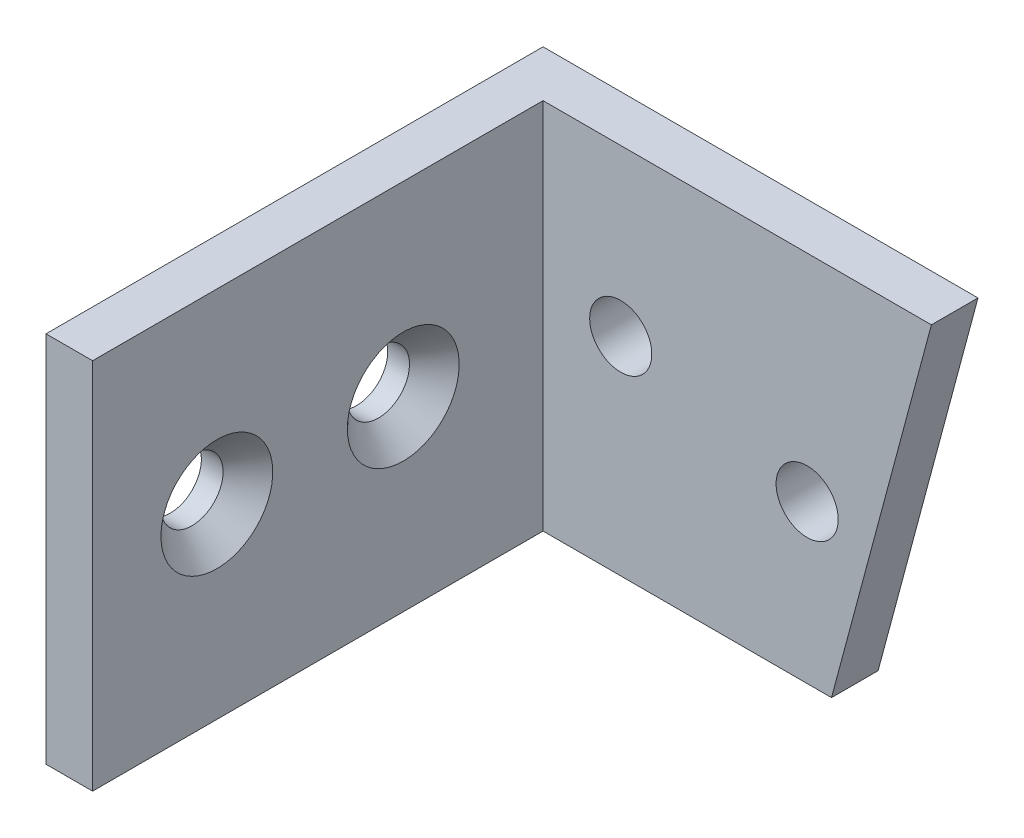
SolidWorks part; units mm, degrees
material "6061 Alloy"
ref_plane "Front Plane" through (0, 0, 0) normal (0, 0, 1) x (1, 0, 0)
ref_plane "Top Plane" through (0, 0, 0) normal (0, 1, 0) x (1, 0, 0)
ref_plane "Right Plane" through (0, 0, 0) normal (1, 0, 0) x (0, 0, -1)
sketch "Sketch1" plane through (0, 0, 0) normal (0, 1, 0) x (1, 0, 0)
  line L0 (0, 0) -> (0, 50.8)
  line L1 (0, 50.8) -> (44.45, 50.8)
  line L2 (4.7625, 0) -> (4.7625, 46.0375)
  line L3 (4.7625, 46.0375) -> (44.45, 46.0375)
  line L4 (0, 0) -> (4.7625, 0)
  line L5 (44.45, 50.8) -> (44.45, 46.0375)
  dimension "D2" = 44.45
  dimension "D3" = 50.8
  dimension "D1" = 4.7625
extrude "Boss-Extrude1" add sketch "Sketch1" along normal blind 38.1
sketch "Sketch2" plane through (0, 0, -50.8) normal (0, 0, -1) x (-1, 0, 0)
  line L0 (0, 24.6103) -> (-44.45, 12.7) construction
  line L1 (0, 38.1) -> (0, 0) construction
  line L2 (-44.45, 38.1) -> (-44.45, 0) construction
  line L3 (-44.45, 0) -> (0, 0) construction
  line L4 (-44.45, 38.1) -> (0, 38.1) construction
  circle A0 centre (-12.7, 21.2074) radius 3.175
  circle A1 centre (-31.75, 16.103) radius 3.175
  dimension "D3" = 6.35
  dimension "D4" = 6.35
  dimension "D5" = 12.7
  dimension "D6" = 19.05
  dimension "D1" = 12.7
  dimension "D2" = 15
extrude "Cut-Extrude1" cut sketch "Sketch2" against normal up to next
sketch "Sketch4" plane through (0, 0, 0) normal (-1, 0, 0) x (0, 0, 1)
  line L0 (0, 38.1) -> (0, 0) construction
  line L1 (-50.8, 38.1) -> (0, 38.1) construction
  circle A0 centre (-12.7, 19.05) radius 3.175
  circle A1 centre (-31.75, 19.05) radius 3.175
  dimension "D1" = 6.35
  dimension "D2" = 6.35
  dimension "D3" = 12.7
  dimension "D4" = 19.05
  dimension "D5" = 19.05
  dimension "D6" = 19.05
extrude "Cut-Extrude2" cut sketch "Sketch4" against normal up to next
sketch "Sketch5" plane through (0, 0, -50.8) normal (0, 0, -1) x (-1, 0, 0)
  line L0 (-34.2411, 0) -> (-44.45, 38.1)
  line L1 (-44.45, 0) -> (0, 0) construction
  line L2 (-44.45, 38.1) -> (-44.45, 0) construction
  dimension "D1" = 0
  dimension "D2" = 15
extrude "Cut-Extrude3" cut sketch "Sketch5" against normal through all and the other way through all
chamfer "Chamfer1" distance 2.54 angle 45 2 edges at (4.7625, 19.05, -9.525) (4.7625, 19.05, -28.575)
